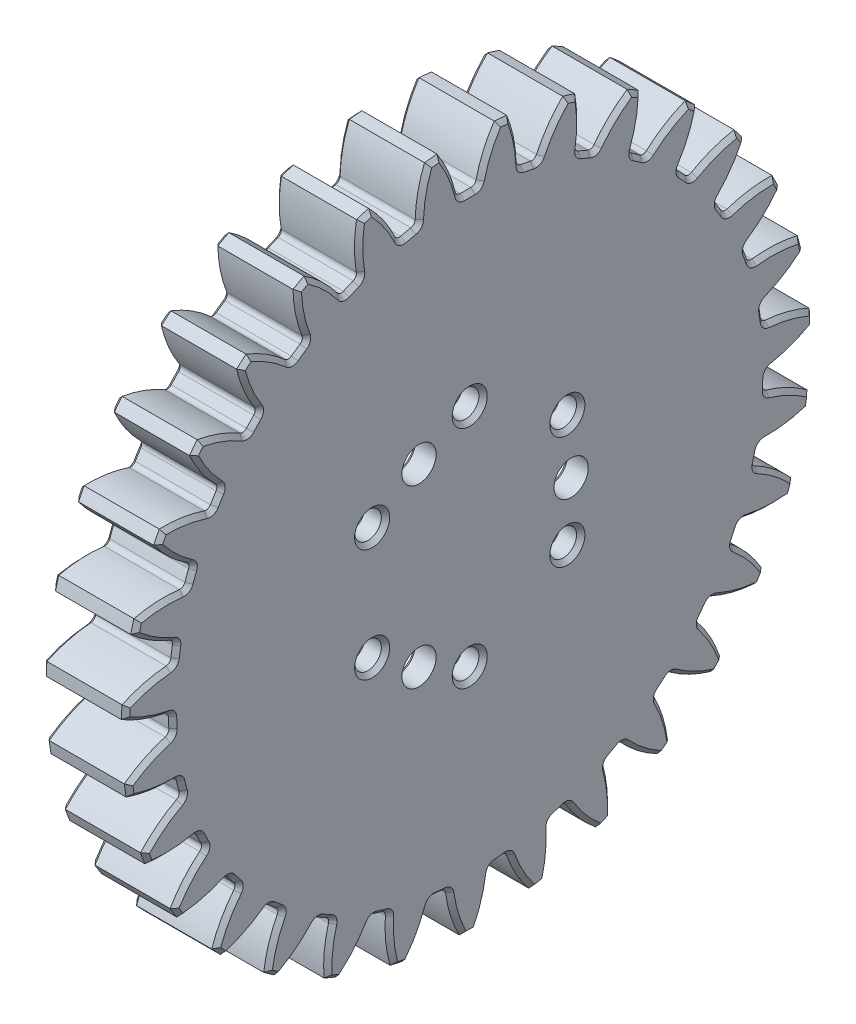
SolidWorks part; units mm, degrees
material "ABS"
ref_plane "Plane1" through (0, 0, 0) normal (0, 0, 1) x (1, 0, 0)
ref_plane "Plane2" through (0, 0, 0) normal (0, 1, 0) x (1, 0, 0)
ref_plane "Plane3" through (0, 0, 0) normal (1, 0, 0) x (0, 0, -1)
other "Configuration Table"
sketch "HoldingSke" plane through (0, 0, 0) normal (0, 1, 0) x (1, 0, 0)
  line L0 (0, 0) -> (0.3429, -0.206)
  line L1 (-15, 0) -> (100, 0) construction
  line L2 (0, 0) -> (-2.1039, 2.3779)
  line L3 (0, 0) -> (-11.863, 4.5341)
  line L4 (0, 0) -> (7.4025, 4.4479)
  line L5 (0, 0) -> (-46.8476, -17.4728)
  line L6 (0, 0) -> (-8.2896, -5.593)
  line L7 (-2.1039, 2.3779) -> (8.6586, 51.2059)
  line L8 (-76.2, 54.61) -> (-71.9, 54.61)
  line L9 (-71.009, 38.7566) -> (-53.1078, 45.2721)
  line L10 (-76.2, 71.12) -> (104.1128, 71.12)
  line L11 (0, 0) -> (-10, 0)
  line L12 (-76.2, 101.6) -> (-76.113, 101.6)
  line L13 (24.9733, 27.94) -> (52.9518, 28.4284)
  line L14 (24.9733, 27.94) -> (24.9743, 27.94)
  line L15 (24.9733, 27.94) -> (100.4006, 29.5858)
  line L16 (-63.627, -2.5) -> (-12.827, -2.5)
  circle A0 centre (0, 0) radius 25
  circle A1 centre (0, 0) radius 35.624
  circle A2 centre (0, 0) radius 37.5
  circle A3 centre (0, 0) radius 25
  dimension "MHD" = 71.248
  dimension "Hub_dia" = 75
  dimension "Bore" = 50
  dimension "MBD" = 50
  dimension "Num_teeth" = 31
  dimension "Pitch" = 0.4
  dimension "Overall_len" = 50
  dimension "Show_teeth" = 31
  dimension "Thickness" = 10
  dimension "OAL" = 50.0001
  dimension "T_dim" = 4.3
  dimension "Ap" = 20
  dimension "H" = 19.05
  dimension "Pitch_radius" = 180.3128
  dimension "Width" = 10
  dimension "Backlash" = 0.087
  dimension "Addendum_fac" = 1
  dimension "Dedendum_fac" = 1.25
  dimension "Clearance_fac" = 0.25
  dimension "Dedendum_add" = 0.001
  dimension "Module" = 2.5
sketch "BasProSke" plane through (0, 0, 0) normal (0, 1, 0) x (1, 0, 0)
  line L0 (-10, 0) -> (60, 0) construction
  line L1 (0, 0) -> (0, 41.25)
  line L2 (0, 0) -> (10, 0)
  line L3 (10, 0) -> (10, 41.25)
  line L4 (10, 41.25) -> (0, 41.25)
  dimension "Thickness" = 10
  dimension "Diameter" = 82.5
revolve "Base-Revolve" add sketch "BasProSke" angle 360 about L0
sketch "TooCutSke" plane through (0, 0, 0) normal (1, 0, 0) x (0, 0, -1)
  line L1 (0, 0) -> (0, 107) construction
  line L2 (0, 0) -> (-2.1149, 38.6922) construction
  line L3 (0, 0) -> (-7.832, 77.0182) construction
  line L4 (-2.1149, 38.6922) -> (-3.916, 38.5091) construction
  arc A0 (1.1478, 35.6055) -> (-1.1478, 35.6055) centre (0, 0) ccw
  arc A1 (3.4407, 41.1317) -> (-3.4407, 41.1317) centre (0, 0) ccw
  circle A2 centre (0, 0) radius 38.75 construction
  circle A3 centre (0, 0) radius 36.4131 construction
  arc A4 (-1.1478, 35.6055) -> (-3.4407, 41.1317) centre (-16.3417, 32.5402) ccw
  arc A5 (3.4407, 41.1317) -> (1.1478, 35.6055) centre (16.3417, 32.5402) ccw
  dimension "Root_dia" = 71.248
  dimension "Overcut_dia" = 82.5508
  dimension "Pitch_dia" = 77.5
  dimension "Base_dia" = 72.8262
  dimension "Flank_rad" = 15.5
  dimension "Half_ang" = 5.806
  dimension "Half_CT" = 1.8104
extrude "ToothCut" cut sketch "TooCutSke" along normal through all
fillet "Breaks" [suppressed] radius 0.05
fillet "RootFillets" radius 0.626 2 edges at (5, 35.6055, -1.1478) (5, 35.6055, 1.1478)
pattern_circular "TeethCuts" count 31 every 11.613 about axis through (-10, 0, 0) along (1, 0, 0) of "ToothCut", "RootFillets", "Breaks"
sketch "HubNeaOneSke" plane through (0, 0, 0) normal (-1, 0, 0) x (0, 0, 1)
  circle A0 centre (0, 0) radius 35.624
  dimension "Diameter" = 71.248
extrude "HubNearOne" [suppressed] add sketch "HubNeaOneSke" along normal blind 40.0001
sketch "HubNeaBotSke" plane through (0, 0, 0) normal (-1, 0, 0) x (0, 0, 1)
  circle A0 centre (0, 0) radius 35.624
  dimension "Diameter" = 71.248
extrude "HubNearBoth" [suppressed] add sketch "HubNeaBotSke" along normal blind 20
ref_plane "FarPln" through (10, 0, 0) normal (1, 0, 0) x (0, 0, -1)
sketch "HubFarSke" plane through (10, 0, 0) normal (1, 0, 0) x (0, 0, -1)
  circle A0 centre (0, 0) radius 35.624
  dimension "Diameter" = 71.248
extrude "HubFar" [suppressed] add sketch "HubFarSke" along normal blind 20
sketch "BorSke" plane through (0, 0, 0) normal (1, 0, 0) x (0, 0, -1)
  circle A0 centre (0, 0) radius 25
  dimension "Diameter" = 50
extrude "Bore" cut sketch "BorSke" along normal mid plane 100.0001
sketch "KeySke" plane through (0, 0, 0) normal (1, 0, 0) x (0, 0, -1)
  line L0 (-8, 0) -> (-8, 29.3)
  line L1 (-8, 29.3) -> (8, 29.3)
  line L2 (8, 29.3) -> (8, 0)
  line L3 (0, 0) -> (0, 34) construction
  line L4 (-8, 0) -> (8, 0)
  dimension "Offset" = 29.3
  dimension "Width" = 16
extrude "Keyway" [suppressed] cut sketch "KeySke" along normal mid plane 100.0001
pattern_circular "Keyway2" [suppressed] count 2 every 90 about axis through (-10, 0, 0) along (1, 0, 0)
sketch "草图3" plane through (10, 0, 0) normal (1, 0, 0) x (0, 0, -1)
  circle A0 centre (0, 0) radius 24.65
  circle A1 centre (0, 0) radius 25 construction
  circle A2 centre (0, 0) radius 25
  dimension "D1" = 49.3
extrude "凸台-拉伸1" add sketch "草图3" against normal up to surface (10 mm away) up to face at (0, 0, -25)
sketch "草图4" plane through (10, 0, 0) normal (1, 0, 0) x (0, 0, -1)
  circle A0 centre (0, 0) radius 24.65 construction
  circle A1 centre (0, 0) radius 24.65
extrude "凸台-拉伸2" add sketch "草图4" against normal blind 3
sketch "草图6" plane through (0, 0, 0) normal (-1, 0, 0) x (0, 0, 1)
  circle A0 centre (0, 0) radius 29.5
  dimension "D1" = 59
extrude "切除-拉伸4" cut sketch "草图6" against normal up to surface (7 mm away) up to face at (7, 0, -24.65)
sketch "草图5" plane through (7, 0, 0) normal (-1, 0, 0) x (0, 0, 1)
  line L0 (0, 0) -> (0, 13.5) construction
  circle A9 centre (0, 0) radius 13.5 construction
  circle A10 centre (0, 13.5) radius 1.6
  circle A16 centre (11.6913, 6.75) radius 1.6
  circle A17 centre (11.6913, -6.75) radius 1.6
  circle A18 centre (0, -13.5) radius 1.6
  circle A19 centre (-11.6913, -6.75) radius 1.6
  circle A20 centre (-11.6913, 6.75) radius 1.6
  point P5 (0, 0)
  point P10 (0, 0)
  dimension "D1" = 27
  dimension "D2" = 3.2
  dimension "D4" = 6
extrude "切除-拉伸3" cut sketch "草图5" against normal through all
chamfer "倒角1" distance 0.5 angle 45 379 edges at (0, 29.2389, -20.3509) (10, 29.2389, -20.3509) (0, 30.5536, -23.8468) (10, 30.5536, -23.8468) (0, 32.9738, -20.3696) (0, 28.7533, -21.269) (10, 28.7533, -21.269) (0, 29.9312, -19.5766) (10, 29.9312, -19.5766) (0, 32.737, -14.0485) (10, 32.737, -14.0485) (0, 34.7285, -17.2083) (10, 34.7285, -17.2083) (0, 36.3992, -13.315) (0, 32.4461, -15.0456) (10, 32.4461, -15.0456) (0, 33.2592, -13.1508) (10, 33.2592, -13.1508) (0, 34.8948, -7.1711) (10, 34.8948, -7.1711) (0, 37.4816, -9.8652) (10, 37.4816, -9.8652) (0, 38.3344, -5.7153) (0, 34.8106, -8.2063) (10, 34.8106, -8.2063) (0, 35.2256, -6.1866) (10, 35.2256, -6.1866) (0, 0, 29.5) (10, 13.5, 1.6) (10, 6.75, -10.0913) (10, -6.75, -10.0913) (10, -13.5, 1.6) (10, -6.75, 13.2913) (10, 6.75, 13.2913) (10, 41.0384, -4.1732) (10, 39.3582, -12.3487) (10, 36.0668, -20.0187) (10, 31.2988, -26.8691) (10, 25.2494, -32.6195) (10, 18.1663, -37.0344) (10, 10.3394, -39.9332) (10, 2.0893, -41.1971) (10, -6.2464, -40.7743) (10, -14.3263, -38.6823) (10, -21.8198, -35.0066) (10, -28.4199, -29.8977) (10, -33.8565, -23.5648) (10, -37.907, -16.2672) (10, -40.4056, -8.3036) (10, -41.25, 0) (10, -40.4056, 8.3036) (10, -37.907, 16.2672) (10, -33.8565, 23.5648) (10, -28.4199, 29.8977) (10, -21.8198, 35.0066) (10, -14.3263, 38.6823) (10, -6.2464, 40.7743) (10, 2.0893, 41.1971) (10, 10.3394, 39.9332) (10, 18.1663, 37.0344) (10, 25.2494, 32.6195) (10, 31.2988, 26.8691) (10, 36.0668, 20.0187) (10, 39.3582, 12.3487) (10, 38.7002, 2.1183) (10, -4.0757, 38.5432) (10, 3.7664, 38.5747) (10, 11.4543, 37.0269) (10, 18.6733, 33.9632) (10, 30.5536, 23.8468) (10, 25.1278, 29.5091) (10, 34.7285, 17.2083) (10, -38.7159, 1.8078) (10, -37.5595, 9.5642) (0, 35.624, 0) (10, 35.624, 0) (10, -30.7439, 23.601) (10, -34.8654, 16.9291) (0, 38.7002, -2.1183) (10, 38.7002, -2.1183) (10, -18.9452, 33.8123) (10, -25.3637, 29.3065) (0, 38.7002, 2.1183) (10, -11.751, 36.9338) (0, 35.7499, -1.0309) (10, 35.7499, -1.0309) (10, -22.0135, -31.8998) (0, 35.7499, 1.0309) (10, 35.7499, 1.0309) (10, -27.9843, -26.8155) (10, -15.1415, -35.6781) (10, -7.6496, -37.9957) (10, -32.8094, -20.6334) (10, -36.2912, -13.6066) (10, -38.2873, -6.0227) (10, 38.3344, -5.7153) (10, 36.3992, -13.315) (0, 41.0384, 4.1732) (10, 28.1985, -26.5902) (10, 32.9738, -20.3696) (10, 22.2687, -31.7222) (10, 41.0384, 4.1732) (10, 15.4272, -35.5555) (10, 7.9542, -37.9331) (10, 0.1555, -38.7578) (10, 37.4816, 9.8652) (0, 39.3582, -12.3487) (0, 36.0668, -20.0187) (0, 34.8948, 7.1711) (10, 34.8948, 7.1711) (0, 31.2988, -26.8691) (0, 38.3344, 5.7153) (10, 38.3344, 5.7153) (0, 37.4816, 9.8652) (0, 35.2256, 6.1866) (10, 35.2256, 6.1866) (0, 25.2494, -32.6195) (0, 34.8106, 8.2063) (10, 34.8106, 8.2063) (0, 18.1663, -37.0344) (0, 32.737, 14.0485) (10, 32.737, 14.0485) (0, 36.3992, 13.315) (10, 36.3992, 13.315) (0, 10.3394, -39.9332) (0, 34.7285, 17.2083) (0, 33.2592, 13.1508) (10, 33.2592, 13.1508) (0, 32.4461, 15.0456) (10, 32.4461, 15.0456) (0, 2.0893, -41.1971) (0, 29.2389, 20.3509) (10, 29.2389, 20.3509) (0, -6.2464, -40.7743) (0, 32.9738, 20.3696) (10, 32.9738, 20.3696) (0, 30.5536, 23.8468) (0, 29.9312, 19.5766) (10, 29.9312, 19.5766) (0, 28.7533, 21.269) (10, 28.7533, 21.269) (0, -14.3263, -38.6823) (0, 24.5438, 25.82) (0, -21.8198, -35.0066) (10, 24.5438, 25.82) (0, 28.1985, 26.5902) (10, 28.1985, 26.5902) (0, 25.1278, 29.5091) (0, 25.3777, 25.201) (0, -28.4199, -29.8977) (10, 25.3777, 25.201) (0, 23.8833, 26.6216) (10, 23.8833, 26.6216) (0, -33.8565, -23.5648) (0, 18.8438, 30.2321) (10, 18.8438, 30.2321) (0, 22.2687, 31.7222) (10, 22.2687, 31.7222) (0, -37.907, -16.2672) (0, 18.6733, 33.9632) (0, 19.7853, 29.7936) (10, 19.7853, 29.7936) (0, 18.0355, 30.8843) (10, 18.0355, 30.8843) (0, -40.4056, -8.3036) (0, 12.3724, 33.4065) (10, 12.3724, 33.4065) (0, -41.25, 0) (0, 15.4272, 35.5555) (10, 15.4272, 35.5555) (0, 11.4543, 37.0269) (0, 13.3829, 33.1665) (10, 13.3829, 33.1665) (0, 11.4494, 33.8826) (10, 11.4494, 33.8826) (0, -40.4056, 8.3036) (0, -37.907, 16.2672) (0, 5.3945, 35.2132) (10, 5.3945, 35.2132) (0, 7.9542, 37.9331) (10, 7.9542, 37.9331) (0, 3.7664, 38.5747) (0, -33.8565, 23.5648) (0, 6.4326, 35.1816) (10, 6.4326, 35.1816) (0, 4.3945, 35.4938) (10, 4.3945, 35.4938) (0, -28.4199, 29.8977) (0, -1.8043, 35.5783) (10, -1.8043, 35.5783) (0, 0.1555, 38.7578) (10, 0.1555, 38.7578) (0, -21.8198, 35.0066) (0, -4.0757, 38.5432) (0, -0.7811, 35.7563) (10, -0.7811, 35.7563) (0, -2.8403, 35.6518) (10, -2.8403, 35.6518) (0, -14.3263, 38.6823) (0, -8.9292, 34.4868) (10, -8.9292, 34.4868) (0, -6.2464, 40.7743) (0, -7.6496, 37.9957) (10, -7.6496, 37.9957) (0, -11.751, 36.9338) (0, -7.9628, 34.8671) (10, -7.9628, 34.8671) (0, -9.9588, 34.3503) (0, 2.0893, 41.1971) (10, -9.9588, 34.3503) (0, 10.3394, 39.9332) (0, -15.6886, 31.9834) (10, -15.6886, 31.9834) (0, -15.1415, 35.6781) (10, -15.1415, 35.6781) (0, -18.9452, 33.8123) (0, 18.1663, 37.0344) (0, -14.8185, 32.5505) (10, -14.8185, 32.5505) (0, -16.6696, 31.6424) (10, -16.6696, 31.6424) (0, 25.2494, 32.6195) (0, -21.8057, 28.1706) (10, -21.8057, 28.1706) (0, 31.2988, 26.8691) (0, -22.0135, 31.8998) (10, -22.0135, 31.8998) (0, -25.3637, 29.3065) (0, -21.0675, 28.9012) (10, -21.0675, 28.9012) (0, -22.698, 27.6391) (10, -22.698, 27.6391) (0, 36.0668, 20.0187) (0, -27.03, 23.2045) (0, 39.3582, 12.3487) (10, -27.03, 23.2045) (0, -27.9843, 26.8155) (10, -27.9843, 26.8155) (0, -30.7439, 23.601) (0, -26.454, 24.0688) (10, -26.454, 24.0688) (0, -27.7971, 22.5043) (10, -27.7971, 22.5043) (0, -31.1477, 17.2884) (10, -31.1477, 17.2884) (0, -32.8094, 20.6334) (10, -32.8094, 20.6334) (0, -34.8654, 16.9291) (0, -30.7575, 18.2509) (10, -30.7575, 18.2509) (0, -31.7581, 16.4481) (10, -31.7581, 16.4481) (0, -33.9903, 10.6645) (10, -33.9903, 10.6645) (0, -36.2912, 13.6066) (10, -36.2912, 13.6066) (0, -37.5595, 9.5642) (0, -33.8018, 11.6859) (10, -33.8018, 11.6859) (0, -34.419, 9.7185) (10, -34.419, 9.7185) (0, -35.4412, 3.604) (10, -35.4412, 3.604) (0, -38.2873, 6.0227) (10, -38.2873, 6.0227) (0, -38.7159, 1.8078) (0, -35.4622, 4.6424) (10, -35.4622, 4.6424) (0, -35.6708, 2.5911) (10, -35.6708, 2.5911) (0, -35.4412, -3.604) (10, -35.4412, -3.604) (0, -38.7159, -1.8078) (10, -38.7159, -1.8078) (0, -38.2873, -6.0227) (0, -35.6708, -2.5911) (10, -35.6708, -2.5911) (0, -35.4622, -4.6424) (10, -35.4622, -4.6424) (0, -33.9903, -10.6645) (10, -33.9903, -10.6645) (0, -37.5595, -9.5642) (10, -37.5595, -9.5642) (0, -36.2912, -13.6066) (0, -34.419, -9.7185) (10, -34.419, -9.7185) (0, -33.8018, -11.6859) (10, -33.8018, -11.6859) (0, -31.1477, -17.2884) (10, -31.1477, -17.2884) (0, -34.8654, -16.9291) (10, -34.8654, -16.9291) (0, -32.8094, -20.6334) (0, -31.7581, -16.4481) (10, -31.7581, -16.4481) (0, -30.7575, -18.2509) (10, -30.7575, -18.2509) (0, -27.03, -23.2045) (10, -27.03, -23.2045) (0, -30.7439, -23.601) (10, -30.7439, -23.601) (0, -27.9843, -26.8155) (0, -27.7971, -22.5043) (10, -27.7971, -22.5043) (0, -26.454, -24.0688) (10, -26.454, -24.0688) (0, -21.8057, -28.1706) (10, -21.8057, -28.1706) (0, -25.3637, -29.3065) (10, -25.3637, -29.3065) (0, -22.0135, -31.8998) (0, -22.698, -27.6391) (10, -22.698, -27.6391) (0, -21.0675, -28.9012) (10, -21.0675, -28.9012) (0, -15.6886, -31.9834) (10, -15.6886, -31.9834) (0, -18.9452, -33.8123) (10, -18.9452, -33.8123) (0, -15.1415, -35.6781) (0, -16.6696, -31.6424) (10, -16.6696, -31.6424) (0, -14.8185, -32.5505) (10, -14.8185, -32.5505) (0, -8.9292, -34.4868) (10, -8.9292, -34.4868) (0, -11.751, -36.9338) (10, -11.751, -36.9338) (0, -7.6496, -37.9957) (0, -9.9588, -34.3503) (10, -9.9588, -34.3503) (0, -7.9628, -34.8671) (10, -7.9628, -34.8671) (0, -1.8043, -35.5783) (10, -1.8043, -35.5783) (0, -4.0757, -38.5432) (10, -4.0757, -38.5432) (0, 0.1555, -38.7578) (0, -2.8403, -35.6518) (10, -2.8403, -35.6518) (0, 41.0384, -4.1732) (0, -0.7811, -35.7563) (10, -0.7811, -35.7563) (0, 5.3945, -35.2132) (10, 5.3945, -35.2132) (0, 3.7664, -38.5747) (10, 3.7664, -38.5747) (0, 7.9542, -37.9331) (0, 4.3945, -35.4938) (10, 4.3945, -35.4938) (0, 6.4326, -35.1816) (10, 6.4326, -35.1816) (0, 12.3724, -33.4065) (10, 12.3724, -33.4065) (0, 11.4543, -37.0269) (10, 11.4543, -37.0269) (0, 15.4272, -35.5555) (0, 11.4494, -33.8826) (10, 11.4494, -33.8826) (0, 13.3829, -33.1665) (10, 13.3829, -33.1665) (0, 18.8438, -30.2321) (10, 18.8438, -30.2321) (0, 18.6733, -33.9632) (10, 18.6733, -33.9632) (0, 22.2687, -31.7222) (0, 18.0355, -30.8843) (10, 18.0355, -30.8843) (0, 19.7853, -29.7936) (10, 19.7853, -29.7936) (0, 24.5438, -25.82) (10, 24.5438, -25.82) (0, 25.1278, -29.5091) (10, 25.1278, -29.5091) (0, 28.1985, -26.5902) (0, 23.8833, -26.6216) (10, 23.8833, -26.6216) (0, 25.3777, -25.201) (10, 25.3777, -25.201)
sketch "草图7" plane through (7, 0, 0) normal (-1, 0, 0) x (0, 0, 1)
  line L7 (6.075, 10.5222) -> (-12.15, 0) construction
  line L8 (-12.15, 0) -> (6.075, -10.5222) construction
  line L9 (6.075, -10.5222) -> (6.075, 10.5222) construction
  circle A8 centre (0, 0) radius 6.075 construction
  circle A9 centre (6.075, 10.5222) radius 2.05
  circle A10 centre (-12.15, 0) radius 2.05
  circle A11 centre (6.075, -10.5222) radius 2.05
  dimension "D4" = 4.1
  dimension "D3" = 12.15
extrude "切除-拉伸5" cut sketch "草图7" against normal through all
chamfer "倒角2" distance 0.5 angle 45 10 edges at (7, 0, -29.5) (7, 6.75, 13.2913) (7, -6.75, 13.2913) (7, -13.5, 1.6) (7, -6.75, -10.0913) (7, 6.75, -10.0913) (7, 13.5, 1.6) (7, -10.5222, 8.125) (7, 0, -10.1) (7, 10.5222, 8.125)
equation "' \"Module@HoldingSke\" = 6.35"
equation "' \"Num_teeth@HoldingSke\" = 12"
equation "' \"Ap@HoldingSke\" =  20"
equation "' \"Ap@HoldingSke\" = 20"
equation "' \"Width@HoldingSke\" = 0.5 * 25.4"
equation "' \"Hub_dia@HoldingSke\"= 1 * 25.4"
equation "' \"Hub_dia@HoldingSke\" = 1 * 25.4"
equation "' \"Overall_len@HoldingSke\" = 1.0 * 25.4"
equation "' \"Bore@HoldingSke\" = 0.75 * 25.4"
equation "' \"T_dim@HoldingSke\" = 0.1 * 25.4"
equation "' \"Width@KeySke\" = 0.25 * 25.4"
equation "' \"Show_teeth@HoldingSke\" = 13"
equation "' \"Backlash@HoldingSke\" = 0.009 * 25.4"
equation "' \"Addendum_fac@HoldingSke\" = 1.0"
equation "' \"Dedendum_fac@HoldingSke\" = 1.25"
equation "' \"Dedendum_add@HoldingSke\" = 0.00005 * 25.4"
equation "' \"Clearance_fac@HoldingSke\" = 0.25"
equation "\"Pitch@HoldingSke\" = 1 / \"Module@HoldingSke\""
equation "\"Overcut_dia@TooCutSke\" = (\"Num_teeth@HoldingSke\" + 2 * \"Addendum_fac@HoldingSke\") / \"Pitch@HoldingSke\" + 0.002 * 25.4"
equation "\"Pitch_dia@TooCutSke\" = \"Num_teeth@HoldingSke\" / \"Pitch@HoldingSke\""
equation "\"Base_dia@TooCutSke\" = \"Num_teeth@HoldingSke\" / \"Pitch@HoldingSke\" * cos((\"Ap@HoldingSke\"  * 3.14159265 / 180))"
equation "\"Root_dia@TooCutSke\" = (\"Num_teeth@HoldingSke\" + 2) / \"Pitch@HoldingSke\" - 2 * (\"Addendum_fac@HoldingSke\" + \"Dedendum_fac@HoldingSke\") / \"Pitch@HoldingSke\" - \"Dedendum_add@HoldingSke\" * 2"
equation "\"Half_ang@TooCutSke\" = 180 / \"Num_teeth@HoldingSke\""
equation "\"Half_CT@TooCutSke\" = \"Num_teeth@HoldingSke\" / \"Pitch@HoldingSke\" * sin((3.14159265 / 2 / \"Num_teeth@HoldingSke\")) / 2 - 7 * \"Backlash@HoldingSke\" / 4"
equation "\"Flank_rad@TooCutSke\" = \"Num_teeth@HoldingSke\" / \"Pitch@HoldingSke\" / 5"
equation "\"Radius@RootFillets\" = \"Clearance_fac@HoldingSke\" / \"Pitch@HoldingSke\" + \"Dedendum_add@HoldingSke\""
equation "\"Break_rad@Breaks\" = 0.02 / \"Pitch@HoldingSke\""
equation "\"Thickness@HoldingSke\" = \"Width@HoldingSke\""
equation "\"OAL@HoldingSke\" = \"Thickness@HoldingSke\""
equation "\"MHD@HoldingSke\" = (\"Num_teeth@HoldingSke\" + 2) / \"Pitch@HoldingSke\" - 2 * (\"Addendum_fac@HoldingSke\" + \"Dedendum_fac@HoldingSke\")  / \"Pitch@HoldingSke\" - \"Dedendum_add@HoldingSke\" * 2"
equation "\"MBD@HoldingSke\" = (\"Num_teeth@HoldingSke\" + 2) / \"Pitch@HoldingSke\" - 2 * (\"Addendum_fac@HoldingSke\" + \"Dedendum_fac@HoldingSke\")  / \"Pitch@HoldingSke\" - \"Dedendum_add@HoldingSke\" * 2 - 0.002 * 25.4"
equation "\"MHD@HoldingSke\" = ((sgn( \"MHD@HoldingSke\" - \"Hub_dia@HoldingSke\" )-1)*( \"MHD@HoldingSke\" - \"Hub_dia@HoldingSke\" ))/-2+ \"Hub_dia@HoldingSke\""
equation "\"MBD@HoldingSke\" = ((sgn( \"MBD@HoldingSke\" - \"Bore@HoldingSke\" )-1)*( \"MBD@HoldingSke\" - \"Bore@HoldingSke\" ))/-2+ \"Bore@HoldingSke\""
equation "\"OAL@HoldingSke\" = ((sgn( \"OAL@HoldingSke\" - \"Overall_len@HoldingSke\" )+1)*( \"OAL@HoldingSke\" - \"Overall_len@HoldingSke\" ))/2 + \"Overall_len@HoldingSke\" + 0.000002 * 25.4"
equation "\"Num_teeth@TeethCuts\" = int( \"Show_teeth@HoldingSke\" ) + 1"
equation "\"Num_teeth@TeethCuts\" = ((sgn( \"Num_teeth@TeethCuts\" - \"Num_teeth@HoldingSke\" )-1)*( \"Num_teeth@TeethCuts\" - \"Num_teeth@HoldingSke\" ))/-2+ \"Num_teeth@HoldingSke\""
equation "\"Num_teeth@TeethCuts\" = ((sgn( \"Num_teeth@TeethCuts\" - 2.0)+1)*( \"Num_teeth@TeethCuts\" - 2.0))/2 +2.0"
equation "\"Angle@TeethCuts\" = 360.0 / \"Num_teeth@HoldingSke\""
equation "\"Diameter@BasProSke\" = (\"Num_teeth@HoldingSke\" + 2 * \"Addendum_fac@HoldingSke\") / \"Pitch@HoldingSke\""
equation "\"Thickness@BasProSke\"  = \"Thickness@HoldingSke\""
equation "' \"Fillet_rad@BasProSke\" =  \"Thickness@HoldingSke\" * 0.05"
equation "' \"Fillet_rad@BasProSke\" = \"Thickness@HoldingSke\" * 0.05"
equation "\"MHD@HoldingSke\" = ((sgn( \"MHD@HoldingSke\" - \"Root_dia@TooCutSke\" )-1)*( \"MHD@HoldingSke\" - \"Root_dia@TooCutSke\" ))/-2+ \"Root_dia@TooCutSke\""
equation "\"Diameter@HubNeaOneSke\" = \"MHD@HoldingSke\""
equation "\"Length@HubNearOne\" = \"OAL@HoldingSke\" - \"Thickness@BasProSke\""
equation "\"Diameter@HubNeaBotSke\" = \"MHD@HoldingSke\""
equation "\"Length@HubNearBoth\" = ( \"OAL@HoldingSke\" - \"Thickness@BasProSke\" ) / 2.0"
equation "\"Thickness@FarPln\" = \"Thickness@BasProSke\""
equation "\"Diameter@HubFarSke\" = \"MHD@HoldingSke\""
equation "\"Length@HubFar\" = ( \"OAL@HoldingSke\" - \"Thickness@BasProSke\" ) / 2.0"
equation "\"Diameter@BorSke\" = \"MBD@HoldingSke\""
equation "\"D1@Bore\" = \"OAL@HoldingSke\" * 2.0"
equation "\"D1@Keyway\" = \"OAL@HoldingSke\" * 2.0"
equation "\"Offset@KeySke\" = \"T_dim@HoldingSke\" + \"MBD@HoldingSke\" / 2.0"
